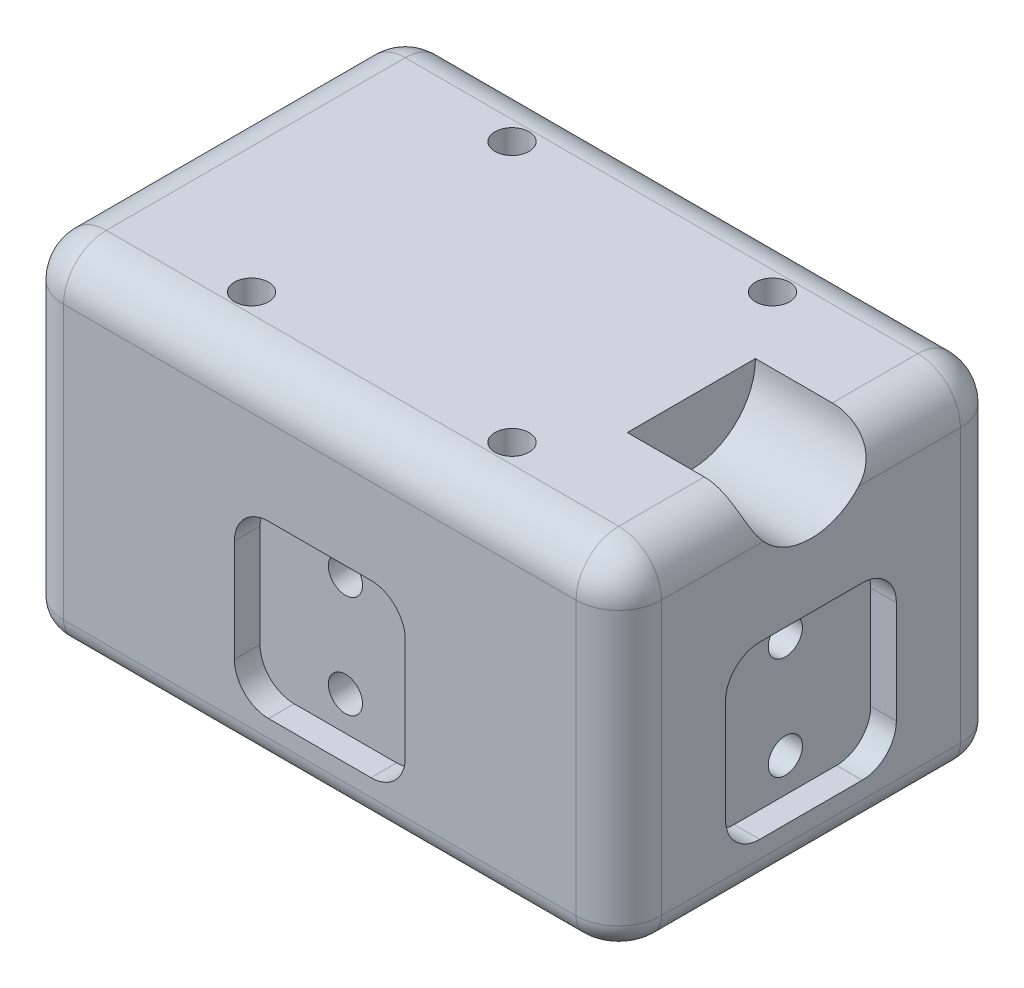
SolidWorks part; units mm, degrees
ref_plane "Front Plane" through (0, 0, 0) normal (0, 0, 1) x (1, 0, 0)
ref_plane "Top Plane" through (0, 0, 0) normal (0, 1, 0) x (1, 0, 0)
ref_plane "Right Plane" through (0, 0, 0) normal (1, 0, 0) x (0, 0, -1)
sketch "Sketch1" plane through (0, 0, 0) normal (0, 1, 0) x (1, 0, 0)
  line L1 (-35, -22.5) -> (35, -22.5)
  line L2 (-35, -22.5) -> (-35, 22.5)
  line L3 (-35, 22.5) -> (35, 22.5)
  line L4 (35, -22.5) -> (35, 22.5)
  line L5 (-35, -22.5) -> (35, 22.5) construction
  line L6 (-35, 22.5) -> (35, -22.5) construction
  point P0 (0, 0)
  dimension "D1" = 70
  dimension "D2" = 45
extrude "Boss-Extrude1" add sketch "Sketch1" along normal blind 40 contours L2 L3 L4 L1
sketch "Sketch2" plane through (0, 0, 0) normal (0, -1, 0) x (1, 0, 0)
  line L0 (-35, 22.5) -> (-35, -22.5) construction
  line L1 (-35, 22.5) -> (35, 22.5) construction
  line L2 (-29.3993, -0.4154) -> (35, -0.4154) construction
  line L3 (35, 22.5) -> (35, -22.5) construction
  line L4 (0, 22.5) -> (0, -22.5) construction
  line L5 (-35, -22.5) -> (35, -22.5) construction
  circle A0 centre (-28, 15.5) radius 2
  circle A3 centre (28, 15.5) radius 2
  circle A6 centre (28, -16.3308) radius 2
  circle A11 centre (-28, -16.3308) radius 2
  dimension "D1" = 4
  dimension "D4" = 7
  dimension "D5" = 7
extrude "Cut-Extrude1" cut sketch "Sketch2" against normal blind 10
sketch "Sketch3" plane through (35, 0, 0) normal (1, 0, 0) x (0, 0, -1)
  line L1 (-6, 5) -> (6, 5)
  line L2 (-10, 9) -> (-10, 21)
  line L3 (-6, 25) -> (6, 25)
  line L4 (10, 9) -> (10, 21)
  line L5 (-10, 5) -> (10, 25) construction
  line L6 (-10, 25) -> (10, 5) construction
  arc A0 (-6, 5) -> (-10, 9) centre (-6, 9) cw
  arc A1 (6, 5) -> (10, 9) centre (6, 9) ccw
  arc A2 (6, 25) -> (10, 21) centre (6, 21) cw
  arc A3 (-10, 21) -> (-6, 25) centre (-6, 21) cw
  point P0 (0, 15)
  dimension "D5" = 4
  dimension "D1" = 20
  dimension "D2" = 20
  dimension "D3" = 0
  dimension "D4" = 15
extrude "Cut-Extrude2" cut sketch "Sketch3" against normal blind 3
sketch "Sketch4" plane through (32, 0, 0) normal (1, 0, 0) x (0, 0, -1)
  line L1 (-10, 15) -> (10, 15) construction
  line L2 (-10, 21) -> (-10, 9) construction
  line L3 (10, 9) -> (10, 21) construction
  circle A0 centre (0, 21) radius 2
  circle A1 centre (0, 9) radius 2
  point P12 (0, 15)
  dimension "D1" = 4
  dimension "D2" = 4
  dimension "D3" = 6
  dimension "D4" = 6
extrude "Cut-Extrude3" cut sketch "Sketch4" against normal blind 10
mirror "Mirror1" about plane through (0, 0, 0) normal (1, 0, 0) of "Cut-Extrude3", "Cut-Extrude2"
sketch "Sketch7" plane through (0, 0, -22.5) normal (0, 0, -1) x (-1, 0, 0)
  line L1 (-6, 5) -> (6, 5)
  line L2 (-10, 9) -> (-10, 21)
  line L3 (-6, 25) -> (6, 25)
  line L4 (10, 9) -> (10, 21)
  line L5 (-10, 5) -> (10, 25) construction
  line L6 (-10, 25) -> (10, 5) construction
  arc A0 (-6, 5) -> (-10, 9) centre (-6, 9) cw
  arc A1 (6, 5) -> (10, 9) centre (6, 9) ccw
  arc A2 (6, 25) -> (10, 21) centre (6, 21) cw
  arc A3 (-10, 21) -> (-6, 25) centre (-6, 21) cw
  point P0 (0, 15)
  dimension "D5" = 4
  dimension "D1" = 20
  dimension "D2" = 20
  dimension "D3" = 0
  dimension "D4" = 15
extrude "Cut-Extrude4" cut sketch "Sketch7" against normal blind 3
sketch "Sketch8" plane through (0, 0, -19.5) normal (0, 0, -1) x (-1, 0, 0)
  line L0 (-6, 5) -> (6, 5) construction
  line L1 (6, 25) -> (-6, 25) construction
  circle A0 centre (0, 21) radius 2
  circle A1 centre (0, 9) radius 2
  dimension "D1" = 4
  dimension "D2" = 4
  dimension "D3" = 4
  dimension "D4" = 4
extrude "Cut-Extrude5" cut sketch "Sketch8" against normal blind 10
mirror "Mirror2" about plane through (0, 0, 0) normal (0, 0, 1) of "Cut-Extrude5", "Cut-Extrude4"
fillet "Fillet1" radius 3 4 edges at (35, 0, 0) (0, 0, -22.5) (-35, 0, 0) (0, 0, 22.5)
fillet "Fillet2" radius 5 8 edges at (34.1213, 0.8787, 21.6213) (34.1213, 0.8787, -21.6213) (-34.1213, 0.8787, -21.6213) (-34.1213, 0.8787, 21.6213) (-35, 21.5, 22.5) (-35, 21.5, -22.5) (35, 21.5, -22.5) (35, 21.5, 22.5)
sketch "Sketch9" plane through (-35, 0, 0) normal (-1, 0, 0) x (0, 0, 1)
  line L1 (-15.5, 28.5) -> (15.5, 28.5)
  line L2 (-15.5, 28.5) -> (-15.5, 35.5)
  line L3 (-15.5, 35.5) -> (15.5, 35.5)
  line L4 (15.5, 28.5) -> (15.5, 35.5)
  line L5 (-15.5, 28.5) -> (15.5, 35.5) construction
  line L6 (-15.5, 35.5) -> (15.5, 28.5) construction
  point P0 (0, 32)
  dimension "D1" = 7
  dimension "D2" = 32
  dimension "D3" = 31
extrude "Cut-Extrude6" cut sketch "Sketch9" against normal blind 55
sketch "Sketch10" plane through (0, 40, 0) normal (0, 1, 0) x (1, 0, 0)
  circle A0 centre (15.25, 15.25) radius 2
  circle A1 centre (15.25, -15.25) radius 2
  circle A2 centre (-15.25, 15.25) radius 2
  circle A3 centre (-15.25, -15.25) radius 2
  dimension "D1" = 4
  dimension "D2" = 4
  dimension "D3" = 4
  dimension "D4" = 4
  dimension "D5" = 30.5
  dimension "D6" = 30.5
  dimension "D7" = 30.5
  dimension "D8" = 30.5
  dimension "D9" = 15.25
  dimension "D10" = 15.25
extrude "Cut-Extrude7" cut sketch "Sketch10" against normal blind 6
sketch "Sketch11" plane through (35, 0, 0) normal (1, 0, 0) x (0, 0, -1)
  circle A0 centre (0, 40) radius 7.5
  dimension "D1" = 15
  dimension "D2" = 40
extrude "Cut-Extrude8" cut sketch "Sketch11" against normal blind 14
fillet "Fillet3" radius 5 9 edges at (35, 40, -12.5) (33.5355, 40, -21.0355) (0, 40, -22.5) (-33.5355, 40, -21.0355) (-35, 40, 0) (-33.5355, 40, 21.0355) (35, 40, 12.5) (33.5355, 40, 21.0355) (0, 40, 22.5)
